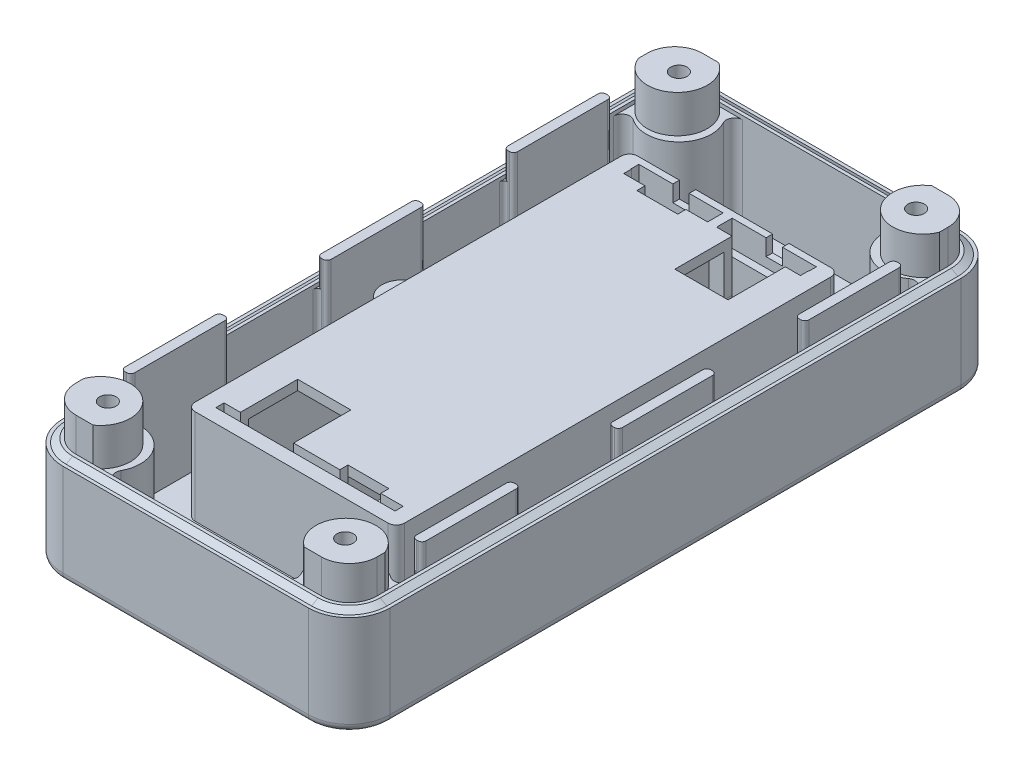
SolidWorks part; units mm, degrees
ref_plane "Front Plane" through (0, 0, 0) normal (0, 0, 1) x (1, 0, 0)
ref_plane "Top Plane" through (0, 0, 0) normal (0, 1, 0) x (1, 0, 0)
ref_plane "Right Plane" through (0, 0, 0) normal (1, 0, 0) x (0, 0, -1)
sketch "Base Sketch" plane through (0, 0, 0) normal (0, 1, 0) x (1, 0, 0)
  line L1 (0, 0) -> (40, 0)
  line L2 (0, 0) -> (0, 79.79)
  line L3 (0, 79.79) -> (40, 79.79)
  line L4 (40, 0) -> (40, 79.79)
extrude "Base" add sketch "Base Sketch" along normal blind 12.3
fillet "Corner Rounds R5" radius 5 4 edges at (0, 6.15, -79.79) (40, 6.15, -79.79) (40, 6.15, 0) (0, 6.15, 0)
shell "Shell" thickness 1.6 removed face at (20, 12.3, -39.895)
sketch "Sketch2" plane through (0, 0, 0) normal (0, 1, 0) x (1, 0, 0)
  circle A0 centre (5.5, 5) radius 4
  circle A1 centre (34.5, 5) radius 4
  circle A2 centre (5.5, 74.79) radius 4
  circle A3 centre (34.5, 74.79) radius 4
extrude "Screw Bosses" add sketch "Sketch2" along normal blind 12.3
sketch "Sketch3" plane through (0, 0, 0) normal (0, 1, 0) x (1, 0, 0)
  line L1 (1.6, 10.5) -> (2.8, 10.5)
  line L2 (1.6, 10.5) -> (1.6, 22.5)
  line L3 (1.6, 22.5) -> (2.8, 22.5)
  line L4 (2.8, 10.5) -> (2.8, 22.5)
  line L6 (1.6, 34.5) -> (2.8, 34.5)
  line L7 (1.6, 34.5) -> (1.6, 46.5)
  line L8 (1.6, 46.5) -> (2.8, 46.5)
  line L9 (2.8, 34.5) -> (2.8, 46.5)
  line L11 (1.6, 57.29) -> (2.8, 57.29)
  line L12 (1.6, 57.29) -> (1.6, 69.29)
  line L13 (1.6, 69.29) -> (2.8, 69.29)
  line L14 (2.8, 57.29) -> (2.8, 69.29)
  line L16 (37.2, 10.5) -> (38.4, 10.5)
  line L17 (37.2, 10.5) -> (37.2, 22.5)
  line L18 (37.2, 22.5) -> (38.4, 22.5)
  line L19 (38.4, 10.5) -> (38.4, 22.5)
  line L21 (37.2, 34.5) -> (38.4, 34.5)
  line L22 (37.2, 34.5) -> (37.2, 46.5)
  line L23 (37.2, 46.5) -> (38.4, 46.5)
  line L24 (38.4, 34.5) -> (38.4, 46.5)
  line L26 (37.2, 57.29) -> (38.4, 57.29)
  line L27 (37.2, 57.29) -> (37.2, 69.29)
  line L28 (37.2, 69.29) -> (38.4, 69.29)
  line L29 (38.4, 57.29) -> (38.4, 69.29)
extrude "Alignment Tabs" add sketch "Sketch3" along normal blind 15.6
fillet "Bottom Edge Round R1" radius 1 8 edges at (1.4645, 0, -1.4645) (20, 0, 0) (38.5355, 0, -1.4645) (40, 0, -39.895) (38.5355, 0, -78.3255) (20, 0, -79.79) (1.4645, 0, -78.3255) (0, 0, -39.895)
fillet "Lug Junction Fillets R1" radius 1 8 edges at (32.3929, 6.95, -78.19) (38.4, 6.95, -73.9012) (7.6071, 6.95, -78.19) (1.6, 6.95, -73.9012) (32.3929, 6.95, -1.6) (38.4, 6.95, -5.8888) (7.6071, 6.95, -1.6) (1.6, 6.95, -5.8888)
fillet "Fillet2" radius 0.5 24 edges at (37.2, 8.6, -69.29) (38.4, 6.95, -69.29) (37.2, 8.6, -57.29) (37.2, 8.6, -46.5) (37.2, 8.6, -34.5) (37.2, 8.6, -22.5) (37.2, 8.6, -10.5) (2.8, 8.6, -69.29) (2.8, 8.6, -57.29) (2.8, 8.6, -46.5) (2.8, 8.6, -34.5) (2.8, 8.6, -22.5) (2.8, 8.6, -10.5) (38.4, 6.95, -57.29) (38.4, 6.95, -46.5) (38.4, 6.95, -34.5) (38.4, 6.95, -22.5) (38.4, 6.95, -10.5) (1.6, 6.95, -69.29) (1.6, 6.95, -57.29) (1.6, 6.95, -46.5) (1.6, 6.95, -34.5) (1.6, 6.95, -22.5) (1.6, 6.95, -10.5)
fillet "Tab Top Corner Fillets R0.5" radius 0.5 12 edges at (38.4, 13.95, -57.29) (38.4, 13.95, -69.29) (38.4, 13.95, -34.5) (38.4, 13.95, -46.5) (38.4, 13.95, -10.5) (38.4, 13.95, -22.5) (1.6, 13.95, -57.29) (1.6, 13.95, -69.29) (1.6, 13.95, -34.5) (1.6, 13.95, -46.5) (1.6, 13.95, -22.5) (1.6, 13.95, -10.5)
sketch "Battery Compartment Block Sketch" plane through (0, 0, 0) normal (0, 1, 0) x (1, 0, 0)
  line L0 (8, 13.75) -> (32, 13.75)
  line L1 (32, 13.75) -> (32, 66.25)
  line L2 (32, 66.25) -> (8, 66.25)
  line L3 (8, 66.25) -> (8, 13.75)
extrude "Battery Compartment Block" add sketch "Battery Compartment Block Sketch" along normal blind 13.2
sketch "Battery Door Opening Sketch" plane through (0, 0, 0) normal (0, 1, 0) x (1, 0, 0)
  line L0 (9.2, 14.95) -> (30.8, 14.95)
  line L1 (30.8, 14.95) -> (30.8, 65.05)
  line L2 (30.8, 65.05) -> (9.2, 65.05)
  line L3 (9.2, 65.05) -> (9.2, 14.95)
extrude "Battery Door Opening" cut sketch "Battery Door Opening Sketch" along normal blind 1.6
sketch "Cell Channels 10.2 x 46.7 Sketch" plane through (0, 0, 0) normal (0, 1, 0) x (1, 0, 0)
  line L0 (9.2, 16.65) -> (19.4, 16.65)
  line L1 (19.4, 16.65) -> (19.4, 63.35)
  line L2 (19.4, 63.35) -> (9.2, 63.35)
  line L3 (9.2, 63.35) -> (9.2, 16.65)
  line L4 (20.6, 16.65) -> (30.8, 16.65)
  line L5 (30.8, 16.65) -> (30.8, 63.35)
  line L6 (30.8, 63.35) -> (20.6, 63.35)
  line L7 (20.6, 63.35) -> (20.6, 16.65)
extrude "Cell Channels 10.2 x 46.7" cut sketch "Cell Channels 10.2 x 46.7 Sketch" along normal blind 12
sketch "Divider Relief (divider 7 tall) Sketch" plane through (0, 0, 0) normal (0, 1, 0) x (1, 0, 0)
  line L0 (19.4, 16.65) -> (20.6, 16.65)
  line L1 (20.6, 16.65) -> (20.6, 63.35)
  line L2 (20.6, 63.35) -> (19.4, 63.35)
  line L3 (19.4, 63.35) -> (19.4, 16.65)
extrude "Divider Relief (divider 7 tall)" cut sketch "Divider Relief (divider 7 tall) Sketch" along normal blind 5
sketch "Clip Slots 0.7 Sketch" plane through (0, 0, 0) normal (0, 1, 0) x (1, 0, 0)
  line L0 (9.05, 14.95) -> (30.95, 14.95)
  line L1 (30.95, 14.95) -> (30.95, 15.65)
  line L2 (30.95, 15.65) -> (9.05, 15.65)
  line L3 (9.05, 15.65) -> (9.05, 14.95)
  line L4 (9.15, 64.35) -> (19.45, 64.35)
  line L5 (19.45, 64.35) -> (19.45, 65.05)
  line L6 (19.45, 65.05) -> (9.15, 65.05)
  line L7 (9.15, 65.05) -> (9.15, 64.35)
  line L8 (20.55, 64.35) -> (30.85, 64.35)
  line L9 (30.85, 64.35) -> (30.85, 65.05)
  line L10 (30.85, 65.05) -> (20.55, 65.05)
  line L11 (20.55, 65.05) -> (20.55, 64.35)
extrude "Clip Slots 0.7 (open to PCB side)" cut sketch "Clip Slots 0.7 Sketch" along normal blind 11.6 from offset 1.6
ref_plane "Contact Opening Plane d15.65" through (0, 0, -15.65) normal (0, 0, 1) x (1, 0, 0)
ref_plane "Floor Inner Plane y1.6" through (0, 1.6, 0) normal (0, 1, 0) x (1, 0, 0)
ref_plane "Door Lip Plane y0.8" through (0, 0.8, 0) normal (0, 1, 0) x (1, 0, 0)
ref_plane "Rim Plane y12.3" through (0, 12.3, 0) normal (0, 1, 0) x (1, 0, 0)
sketch "M2 Pilot Holes 1.6 x 6 (from rim) Sketch" plane through (0, 12.3, 0) normal (0, 1, 0) x (1, 0, 0)
  circle A0 centre (5.5, 5) radius 0.8
  circle A1 centre (34.5, 5) radius 0.8
  circle A2 centre (5.5, 74.79) radius 0.8
  circle A3 centre (34.5, 74.79) radius 0.8
extrude "M2 Pilot Holes 1.6 x 6 (from rim)" cut sketch "M2 Pilot Holes 1.6 x 6 (from rim) Sketch" against normal blind 6
sketch "Clip Stops 0.35 (door end of slots) Sketch" plane through (0, 1.6, 0) normal (0, 1, 0) x (1, 0, 0)
  line L0 (9.05, 14.95) -> (16.7, 14.95)
  line L1 (16.7, 14.95) -> (16.7, 15.65)
  line L2 (16.7, 15.65) -> (9.05, 15.65)
  line L3 (9.05, 15.65) -> (9.05, 14.95)
  line L4 (23.3, 14.95) -> (30.95, 14.95)
  line L5 (30.95, 14.95) -> (30.95, 15.65)
  line L6 (30.95, 15.65) -> (23.3, 15.65)
  line L7 (23.3, 15.65) -> (23.3, 14.95)
  line L8 (9.15, 64.35) -> (19.45, 64.35)
  line L9 (19.45, 64.35) -> (19.45, 65.05)
  line L10 (19.45, 65.05) -> (9.15, 65.05)
  line L11 (9.15, 65.05) -> (9.15, 64.35)
  line L12 (20.55, 64.35) -> (30.85, 64.35)
  line L13 (30.85, 64.35) -> (30.85, 65.05)
  line L14 (30.85, 65.05) -> (20.55, 65.05)
  line L15 (20.55, 65.05) -> (20.55, 64.35)
extrude "Clip Stops 0.35 (door end of slots)" add sketch "Clip Stops 0.35 (door end of slots) Sketch" along normal blind 0.35
sketch "Contact Openings near (U open to PCB) Sketch" plane through (0, 0, -15.65) normal (0, 0, 1) x (1, 0, 0)
  line L0 (16.8, 6.95) -> (16.8, 13.5)
  line L1 (16.8, 13.5) -> (11.8, 13.5)
  line L2 (11.8, 13.5) -> (11.8, 6.95)
  line L3 (28.2, 6.95) -> (28.2, 13.5)
  line L4 (28.2, 13.5) -> (23.2, 13.5)
  line L5 (23.2, 13.5) -> (23.2, 6.95)
  arc A0 (11.8, 6.95) -> (16.8, 6.95) centre (14.3, 6.95) ccw
  arc A1 (23.2, 6.95) -> (28.2, 6.95) centre (25.7, 6.95) ccw
extrude "Contact Openings near (U open to PCB)" cut sketch "Contact Openings near (U open to PCB) Sketch" against normal blind 1
ref_plane "Contact Opening Plane d63.35" through (0, 0, -63.35) normal (0, 0, 1) x (1, 0, 0)
sketch "Contact Openings far (U open to PCB) Sketch" plane through (0, 0, -63.35) normal (0, 0, 1) x (1, 0, 0)
  line L0 (16.8, 6.95) -> (16.8, 13.5)
  line L1 (16.8, 13.5) -> (11.8, 13.5)
  line L2 (11.8, 13.5) -> (11.8, 6.95)
  line L3 (28.2, 6.95) -> (28.2, 13.5)
  line L4 (28.2, 13.5) -> (23.2, 13.5)
  line L5 (23.2, 13.5) -> (23.2, 6.95)
  arc A0 (11.8, 6.95) -> (16.8, 6.95) centre (14.3, 6.95) ccw
  arc A1 (23.2, 6.95) -> (28.2, 6.95) centre (25.7, 6.95) ccw
extrude "Contact Openings far (U open to PCB)" cut sketch "Contact Openings far (U open to PCB) Sketch" against normal blind 1
sketch "Spring Windows 5x6 (back wall) Sketch" plane through (0, 0, 0) normal (0, 1, 0) x (1, 0, 0)
  line L0 (11.8, 16.65) -> (16.8, 16.65)
  line L1 (16.8, 16.65) -> (16.8, 22.65)
  line L2 (16.8, 22.65) -> (11.8, 22.65)
  line L3 (11.8, 22.65) -> (11.8, 16.65)
  line L4 (23.2, 57.35) -> (28.2, 57.35)
  line L5 (28.2, 57.35) -> (28.2, 63.35)
  line L6 (28.2, 63.35) -> (23.2, 63.35)
  line L7 (23.2, 63.35) -> (23.2, 57.35)
extrude "Spring Windows 5x6 (back wall)" cut sketch "Spring Windows 5x6 (back wall) Sketch" along normal through all
ref_plane "Solder Window Plane y10" through (0, 10, 0) normal (0, 1, 0) x (1, 0, 0)
sketch "Solder Access Windows (+ / - plates) Sketch" plane through (0, 10, 0) normal (0, 1, 0) x (1, 0, 0)
  line L0 (9.15, 64.35) -> (19.45, 64.35)
  line L1 (19.45, 64.35) -> (19.45, 66.25)
  line L2 (19.45, 66.25) -> (9.15, 66.25)
  line L3 (9.15, 66.25) -> (9.15, 64.35)
  line L4 (20.55, 64.35) -> (30.85, 64.35)
  line L5 (30.85, 64.35) -> (30.85, 66.25)
  line L6 (30.85, 66.25) -> (20.55, 66.25)
  line L7 (20.55, 66.25) -> (20.55, 64.35)
extrude "Solder Access Windows (+ / - plates)" cut sketch "Solder Access Windows (+ / - plates) Sketch" along normal blind 3.2
sketch "Compartment Walls +0.8 (2.0 thick) Sketch" plane through (0, 1.6, 0) normal (0, 1, 0) x (1, 0, 0)
  line L0 (7.2, 12.95) -> (32.8, 12.95)
  line L1 (32.8, 12.95) -> (32.8, 67.05)
  line L2 (32.8, 67.05) -> (7.2, 67.05)
  line L3 (7.2, 67.05) -> (7.2, 12.95)
  line L4 (8, 13.75) -> (32, 13.75)
  line L5 (32, 13.75) -> (32, 66.25)
  line L6 (32, 66.25) -> (8, 66.25)
  line L7 (8, 66.25) -> (8, 13.75)
extrude "Compartment Walls +0.8 (2.0 thick)" add sketch "Compartment Walls +0.8 (2.0 thick) Sketch" along normal blind 11.6
fillet "Compartment Outer Corners R1" radius 1 4 edges at (7.2, 7.4, -67.05) (32.8, 7.4, -67.05) (32.8, 7.4, -12.95) (7.2, 7.4, -12.95)
sketch "Clip Slots widened to 0.9 (above floor) Sketch" plane through (0, 1.6, 0) normal (0, 1, 0) x (1, 0, 0)
  line L0 (9.05, 14.75) -> (30.95, 14.75)
  line L1 (30.95, 14.75) -> (30.95, 15)
  line L2 (30.95, 15) -> (9.05, 15)
  line L3 (9.05, 15) -> (9.05, 14.75)
  line L4 (9.15, 65) -> (19.45, 65)
  line L5 (19.45, 65) -> (19.45, 65.25)
  line L6 (19.45, 65.25) -> (9.15, 65.25)
  line L7 (9.15, 65.25) -> (9.15, 65)
  line L8 (20.55, 65) -> (30.85, 65)
  line L9 (30.85, 65) -> (30.85, 65.25)
  line L10 (30.85, 65.25) -> (20.55, 65.25)
  line L11 (20.55, 65.25) -> (20.55, 65)
extrude "Clip Slots widened to 0.9 (above floor)" cut sketch "Clip Slots widened to 0.9 (above floor) Sketch" along normal blind 11.6
sketch "Clip Stops 0.9 (near one solid) Sketch" plane through (0, 1.6, 0) normal (0, 1, 0) x (1, 0, 0)
  line L0 (9.05, 14.75) -> (30.95, 14.75)
  line L1 (30.95, 14.75) -> (30.95, 15.65)
  line L2 (30.95, 15.65) -> (9.05, 15.65)
  line L3 (9.05, 15.65) -> (9.05, 14.75)
  line L4 (9.15, 64.35) -> (19.45, 64.35)
  line L5 (19.45, 64.35) -> (19.45, 65.25)
  line L6 (19.45, 65.25) -> (9.15, 65.25)
  line L7 (9.15, 65.25) -> (9.15, 64.35)
  line L8 (20.55, 64.35) -> (30.85, 64.35)
  line L9 (30.85, 64.35) -> (30.85, 65.25)
  line L10 (30.85, 65.25) -> (20.55, 65.25)
  line L11 (20.55, 65.25) -> (20.55, 64.35)
extrude "Clip Stops 0.9 (near one solid)" add sketch "Clip Stops 0.9 (near one solid) Sketch" along normal blind 0.35
sketch "Spring Opening 6.5 near (series spring) Sketch" plane through (0, 0, -15.65) normal (0, 0, 1) x (1, 0, 0)
  line L0 (17.55, 6.95) -> (17.55, 13.5)
  line L1 (17.55, 13.5) -> (11.05, 13.5)
  line L2 (11.05, 13.5) -> (11.05, 6.95)
  arc A0 (11.05, 6.95) -> (17.55, 6.95) centre (14.3, 6.95) ccw
extrude "Spring Opening 6.5 near (series spring)" cut sketch "Spring Opening 6.5 near (series spring) Sketch" against normal blind 1
sketch "Spring Opening 6.5 far (- spring) Sketch" plane through (0, 0, -63.35) normal (0, 0, 1) x (1, 0, 0)
  line L0 (28.95, 6.95) -> (28.95, 13.5)
  line L1 (28.95, 13.5) -> (22.45, 13.5)
  line L2 (22.45, 13.5) -> (22.45, 6.95)
  arc A0 (22.45, 6.95) -> (28.95, 6.95) centre (25.7, 6.95) ccw
extrude "Spring Opening 6.5 far (- spring)" cut sketch "Spring Opening 6.5 far (- spring) Sketch" against normal blind 1
sketch "Spring Windows widened to 6.5 Sketch" plane through (0, 0, 0) normal (0, 1, 0) x (1, 0, 0)
  line L0 (11.05, 16.65) -> (17.55, 16.65)
  line L1 (17.55, 16.65) -> (17.55, 22.65)
  line L2 (17.55, 22.65) -> (11.05, 22.65)
  line L3 (11.05, 22.65) -> (11.05, 16.65)
  line L4 (22.45, 57.35) -> (28.95, 57.35)
  line L5 (28.95, 57.35) -> (28.95, 63.35)
  line L6 (28.95, 63.35) -> (22.45, 63.35)
  line L7 (22.45, 63.35) -> (22.45, 57.35)
extrude "Spring Windows widened to 6.5" cut sketch "Spring Windows widened to 6.5 Sketch" along normal through all
sketch "Door Screw Lug 5 (centred) Sketch" plane through (0, 1.6, 0) normal (0, 1, 0) x (1, 0, 0)
  circle A0 centre (6.5, 40) radius 2.5
extrude "Door Screw Lug 5 (centred)" add sketch "Door Screw Lug 5 (centred) Sketch" along normal blind 9.4
sketch "Door Screw Pilot 1.6 x 9 Sketch" plane through (0, 1.6, 0) normal (0, 1, 0) x (1, 0, 0)
  circle A0 centre (6.5, 40) radius 0.8
extrude "Door Screw Pilot 1.6 x 9" cut sketch "Door Screw Pilot 1.6 x 9 Sketch" along normal blind 9
sketch "Door Hook Pocket (x+ long edge) Sketch" plane through (0, 0.8, 0) normal (0, 1, 0) x (1, 0, 0)
  line L0 (30.75, 16.85) -> (31.7, 16.85)
  line L1 (31.7, 16.85) -> (31.7, 63.15)
  line L2 (31.7, 63.15) -> (30.75, 63.15)
  line L3 (30.75, 63.15) -> (30.75, 16.85)
extrude "Door Hook Pocket (x+ long edge, to y1.6)" cut sketch "Door Hook Pocket (x+ long edge) Sketch" along normal blind 0.8
sketch "+/- Slot Ends flush (10.25) Sketch" plane through (0, 1.6, 0) normal (0, 1, 0) x (1, 0, 0)
  line L0 (8.9, 64.3) -> (9.2, 64.3)
  line L1 (9.2, 64.3) -> (9.2, 65.3)
  line L2 (9.2, 65.3) -> (8.9, 65.3)
  line L3 (8.9, 65.3) -> (8.9, 64.3)
  line L4 (30.8, 64.3) -> (31.1, 64.3)
  line L5 (31.1, 64.3) -> (31.1, 65.3)
  line L6 (31.1, 65.3) -> (30.8, 65.3)
  line L7 (30.8, 65.3) -> (30.8, 64.3)
extrude "+/- Slot Ends flush (10.25)" add sketch "+/- Slot Ends flush (10.25) Sketch" along normal blind 11.6
sketch "Series Slot widened to 1.0 Sketch" plane through (0, 1.6, 0) normal (0, 1, 0) x (1, 0, 0)
  line L0 (9.05, 14.65) -> (30.95, 14.65)
  line L1 (30.95, 14.65) -> (30.95, 14.8)
  line L2 (30.95, 14.8) -> (9.05, 14.8)
  line L3 (9.05, 14.8) -> (9.05, 14.65)
extrude "Series Slot widened to 1.0" cut sketch "Series Slot widened to 1.0 Sketch" along normal blind 11.6
sketch "+/- Slots widened to 1.0 Sketch" plane through (0, 1.6, 0) normal (0, 1, 0) x (1, 0, 0)
  line L0 (9.2, 65.2) -> (19.45, 65.2)
  line L1 (19.45, 65.2) -> (19.45, 65.35)
  line L2 (19.45, 65.35) -> (9.2, 65.35)
  line L3 (9.2, 65.35) -> (9.2, 65.2)
  line L4 (20.55, 65.2) -> (30.8, 65.2)
  line L5 (30.8, 65.2) -> (30.8, 65.35)
  line L6 (30.8, 65.35) -> (20.55, 65.35)
  line L7 (20.55, 65.35) -> (20.55, 65.2)
extrude "+/- Slots widened to 1.0" cut sketch "+/- Slots widened to 1.0 Sketch" along normal blind 11.6
sketch "Clip Stops 1.0 Sketch" plane through (0, 1.6, 0) normal (0, 1, 0) x (1, 0, 0)
  line L0 (9, 14.6) -> (31, 14.6)
  line L1 (31, 14.6) -> (31, 15.7)
  line L2 (31, 15.7) -> (9, 15.7)
  line L3 (9, 15.7) -> (9, 14.6)
  line L4 (9, 64.3) -> (19.5, 64.3)
  line L5 (19.5, 64.3) -> (19.5, 65.4)
  line L6 (19.5, 65.4) -> (9, 65.4)
  line L7 (9, 65.4) -> (9, 64.3)
  line L8 (20.5, 64.3) -> (31, 64.3)
  line L9 (31, 64.3) -> (31, 65.4)
  line L10 (31, 65.4) -> (20.5, 65.4)
  line L11 (20.5, 65.4) -> (20.5, 64.3)
extrude "Clip Stops 1.0" add sketch "Clip Stops 1.0 Sketch" along normal blind 0.35
ref_plane "Compartment Top Plane y13.2" through (0, 13.2, 0) normal (0, 1, 0) x (1, 0, 0)
sketch "Solder Leg Notches 2x2 (+ / - clips) Sketch" plane through (0, 13.2, 0) normal (0, 1, 0) x (1, 0, 0)
  line L0 (13.3, 65.3) -> (15.3, 65.3)
  line L1 (15.3, 65.3) -> (15.3, 67.1)
  line L2 (15.3, 67.1) -> (13.3, 67.1)
  line L3 (13.3, 67.1) -> (13.3, 65.3)
  line L4 (24.7, 65.3) -> (26.7, 65.3)
  line L5 (26.7, 65.3) -> (26.7, 67.1)
  line L6 (26.7, 67.1) -> (24.7, 67.1)
  line L7 (24.7, 67.1) -> (24.7, 65.3)
extrude "Solder Leg Notches 2x2 (+ / - clips)" cut sketch "Solder Leg Notches 2x2 (+ / - clips) Sketch" against normal blind 2
chamfer "Chamfer2" distance 1 angle 45 1 edges at (30.8, 1.6, -40)
sketch "PCB Corner Guides R3.663 Sketch" plane through (0, 12.3, 0) normal (0, 1, 0) x (1, 0, 0)
  circle A0 centre (5, 4.6) radius 3.663
  circle A1 centre (35, 4.6) radius 3.663
  circle A2 centre (5, 75.1) radius 3.663
  circle A3 centre (35, 75.1) radius 3.663
extrude "PCB Corner Guides R3.663 (top y16.9, 0.4 gap)" add sketch "PCB Corner Guides R3.663 Sketch" along normal blind 4.6
sketch "Guide Trim (top cover cavity) Sketch" plane through (0, 12.3, 0) normal (0, 1, 0) x (1, 0, 0)
  line L0 (5, 1.5) -> (35, 1.5)
  line L1 (38.5, 5) -> (38.5, 74.79)
  line L2 (35, 78.29) -> (5, 78.29)
  line L3 (1.5, 74.79) -> (1.5, 5)
  arc A0 (35, 1.5) -> (38.5, 5) centre (35, 5) ccw
  arc A1 (38.5, 74.79) -> (35, 78.29) centre (35, 74.79) ccw
  arc A2 (5, 78.29) -> (1.5, 74.79) centre (5, 74.79) ccw
  arc A3 (1.5, 5) -> (5, 1.5) centre (5, 5) ccw
extrude "Guide Trim (top cover cavity)" cut sketch "Guide Trim (top cover cavity) Sketch" along normal blind 5 flip side to cut
ref_plane "Guide Top Plane y17.3" through (0, 17.3, 0) normal (0, 1, 0) x (1, 0, 0)
sketch "M2 Pilot through guides 1.6 x 11 Sketch" plane through (0, 17.3, 0) normal (0, 1, 0) x (1, 0, 0)
  circle A0 centre (5.5, 5) radius 0.8
  circle A1 centre (34.5, 5) radius 0.8
  circle A2 centre (5.5, 74.79) radius 0.8
  circle A3 centre (34.5, 74.79) radius 0.8
extrude "M2 Pilot through guides 1.6 x 11" cut sketch "M2 Pilot through guides 1.6 x 11 Sketch" against normal blind 11
sketch "M2 Bores 2.0 (guides) Sketch" plane through (0, 17.3, 0) normal (0, 1, 0) x (1, 0, 0)
  circle A0 centre (5.5, 5) radius 1
  circle A1 centre (34.5, 5) radius 1
  circle A2 centre (5.5, 74.79) radius 1
  circle A3 centre (34.5, 74.79) radius 1
extrude "M2 Bores 2.0 (guides)" cut sketch "M2 Bores 2.0 (guides) Sketch" against normal blind 11
sketch "M2 Bore 2.0 (door lug) Sketch" plane through (0, 1.6, 0) normal (0, 1, 0) x (1, 0, 0)
  circle A0 centre (6.5, 40) radius 1
extrude "M2 Bore 2.0 (door lug)" cut sketch "M2 Bore 2.0 (door lug) Sketch" along normal blind 9
sketch "Rim Lip Ring 0.462 Sketch" plane through (0, 12.3, 0) normal (0, 1, 0) x (1, 0, 0)
  line L0 (5, 0) -> (35, 0)
  line L1 (40, 5) -> (40, 74.79)
  line L2 (35, 79.79) -> (5, 79.79)
  line L3 (0, 74.79) -> (0, 5)
  line L4 (5, 1.6) -> (35, 1.6)
  line L5 (38.4, 5) -> (38.4, 74.79)
  line L6 (35, 78.19) -> (5, 78.19)
  line L7 (1.6, 74.79) -> (1.6, 5)
  arc A0 (35, 0) -> (40, 5) centre (35, 5) ccw
  arc A1 (40, 74.79) -> (35, 79.79) centre (35, 74.79) ccw
  arc A2 (5, 79.79) -> (0, 74.79) centre (5, 74.79) ccw
  arc A3 (0, 5) -> (5, 0) centre (5, 5) ccw
  arc A4 (35, 1.6) -> (38.4, 5) centre (35, 5) ccw
  arc A5 (38.4, 74.79) -> (35, 78.19) centre (35, 74.79) ccw
  arc A6 (5, 78.19) -> (1.6, 74.79) centre (5, 74.79) ccw
  arc A7 (1.6, 5) -> (5, 1.6) centre (5, 5) ccw
extrude "Rim Lip Ring 0.462" add sketch "Rim Lip Ring 0.462 Sketch" along normal blind 0.4619
ref_plane "Lip Top Plane" through (0, 12.7619, 0) normal (0, 1, 0) x (1, 0, 0)
sketch "Rim Lip 30deg + 0.4 flats Sketch" plane through (0, 12.7619, 0) normal (0, 1, 0) x (1, 0, 0)
  line L0 (5, 1.2) -> (35, 1.2)
  line L1 (38.8, 5) -> (38.8, 74.79)
  line L2 (35, 78.59) -> (5, 78.59)
  line L3 (1.2, 74.79) -> (1.2, 5)
  arc A0 (35, 1.2) -> (38.8, 5) centre (35, 5) ccw
  arc A1 (38.8, 74.79) -> (35, 78.59) centre (35, 74.79) ccw
  arc A2 (5, 78.59) -> (1.2, 74.79) centre (5, 74.79) ccw
  arc A3 (1.2, 5) -> (5, 1.2) centre (5, 5) ccw
extrude "Rim Lip 30deg + 0.4 flats" cut sketch "Rim Lip 30deg + 0.4 flats Sketch" against normal blind 0.4619 draft 60 flip side to cut
sketch "Guide 0.1 Clearance Sketch" plane through (0, 12.7619, 0) normal (0, 1, 0) x (1, 0, 0)
  line L0 (5, 1.6) -> (35, 1.6)
  line L1 (38.4, 5) -> (38.4, 74.79)
  line L2 (35, 78.19) -> (5, 78.19)
  line L3 (1.6, 74.79) -> (1.6, 5)
  arc A0 (35, 1.6) -> (38.4, 5) centre (35, 5) ccw
  arc A1 (38.4, 74.79) -> (35, 78.19) centre (35, 74.79) ccw
  arc A2 (5, 78.19) -> (1.6, 74.79) centre (5, 74.79) ccw
  arc A3 (1.6, 5) -> (5, 1.6) centre (5, 5) ccw
extrude "Guide 0.1 Clearance to top cover walls" cut sketch "Guide 0.1 Clearance Sketch" along normal through all flip side to cut
sketch "Door Ear Recess (0.15 around the ear) Sketch" plane through (0, 0, 0) normal (0, 1, 0) x (1, 0, 0)
  line L0 (9.2, 48.2236) -> (9.3, 48.2236)
  line L1 (9.3, 48.2236) -> (9.3, 31.7764)
  line L2 (9.3, 31.7764) -> (9.2, 31.7764)
  arc A0 (9.2, 31.7764) -> (5.5768, 36.4687) centre (4.35, 31.7764) ccw
  arc A1 (5.5768, 36.4687) -> (5.5768, 43.5313) centre (6.5, 40) cw
  arc A2 (5.5768, 43.5313) -> (9.2, 48.2236) centre (4.35, 48.2236) ccw
extrude "Door Ear Recess (0.15 around the ear)" cut sketch "Door Ear Recess (0.15 around the ear) Sketch" along normal blind 1.6
sketch "Ear Recess Cap 0.8 (lug covered inside) Sketch" plane through (0, 1.6, 0) normal (0, 1, 0) x (1, 0, 0)
  line L0 (2.82, 31.6) -> (7.6, 31.6)
  line L1 (7.6, 31.6) -> (7.6, 48.4)
  line L2 (7.6, 48.4) -> (2.82, 48.4)
  line L3 (2.82, 48.4) -> (2.82, 31.6)
  circle A0 centre (6.5, 40) radius 1
extrude "Ear Recess Cap 0.8 (lug covered inside)" add sketch "Ear Recess Cap 0.8 (lug covered inside) Sketch" along normal blind 0.8
fillet "Door Cutout Corners R1.15" radius 1.15 4 edges at (9.2, 0.8, -65.05) (30.8, 0.8, -65.05) (30.8, 0.8, -14.95) (9.2, 0.8, -14.95)
fillet "Door Lug + Base Vertical Edges R1" radius 1 6 edges at (2.82, 2, -48.4) (2.82, 2, -31.6) (7.2, 2, -48.4) (7.2, 2, -31.6) (7.2, 6.7, -42.4) (7.2, 6.7, -37.6)
